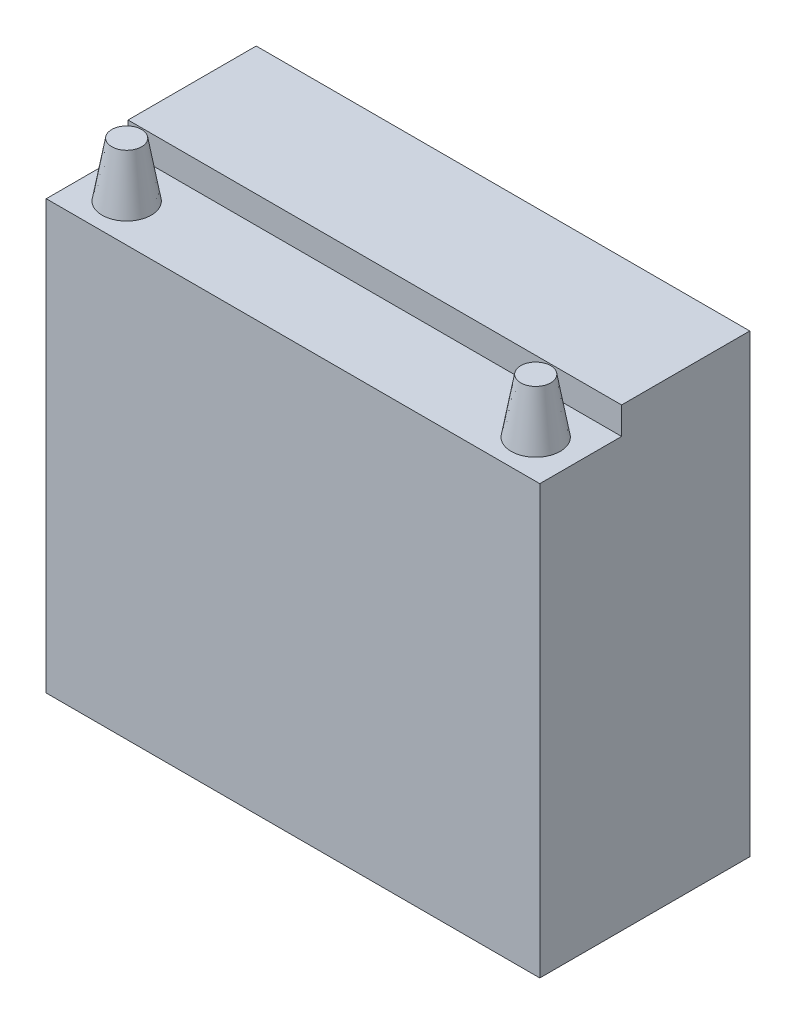
SolidWorks part; units mm, degrees
ref_plane "Plano frontal" through (0, 0, 0) normal (0, 0, 1) x (1, 0, 0)
ref_plane "Plano superior" through (0, 0, 0) normal (0, 1, 0) x (1, 0, 0)
ref_plane "Plano direito" through (0, 0, 0) normal (1, 0, 0) x (0, 0, -1)
ref_plane "Plano1" through (0, 0, -45.1693) normal (0, 0, -1) x (-1, 0, 0)
sketch "Esboço1" plane through (0, 0, -45.1693) normal (0, 0, -1) x (-1, 0, 0)
  line L0 (77, 0) -> (77, 167)
  line L1 (77, 167) -> (-104, 167)
  line L2 (-104, 167) -> (-104, 0)
  line L3 (-104, 0) -> (77, 0)
extrude "Ressalto-extrusão1" add sketch "Esboço1" against normal blind 77
sketch "Esboço2" plane through (-77, 0, 0) normal (-1, 0, 0) x (0, 0, 1)
  line L0 (1.8307, 167) -> (1.8307, 157)
  line L1 (1.8307, 157) -> (31.8307, 157)
  line L2 (31.8307, 157) -> (31.8307, 167)
  line L3 (31.8307, 167) -> (1.8307, 167)
extrude "Corte-extrusão1" cut sketch "Esboço2" against normal through all
ref_plane "Plano2" through (0, 0, 17.8307) normal (0, 0, -1) x (-1, 0, 0)
sketch "Esboço3" plane through (0, 0, 17.8307) normal (0, 0, -1) x (-1, 0, 0)
  line L0 (-97.5, 157) -> (-88.5, 157)
  line L1 (-88.5, 157) -> (-88.5, 177)
  line L2 (-88.5, 177) -> (-93.9735, 177)
  line L3 (-93.9735, 177) -> (-97.5, 157)
  line L4 (-88.5, 157) -> (-88.5, 177) construction
revolve "Revolução1" add sketch "Esboço3" angle 360 about L4 reverse direction yes
sketch "Esboço4" plane through (0, 0, 17.8307) normal (0, 0, -1) x (-1, 0, 0)
  line L0 (52.5, 157) -> (61.5, 157)
  line L1 (61.5, 157) -> (61.5, 177)
  line L2 (61.5, 177) -> (56.0265, 177)
  line L3 (56.0265, 177) -> (52.5, 157)
  line L4 (61.5, 157) -> (61.5, 177) construction
revolve "Revolução2" add sketch "Esboço4" angle 360 about L4 reverse direction yes
